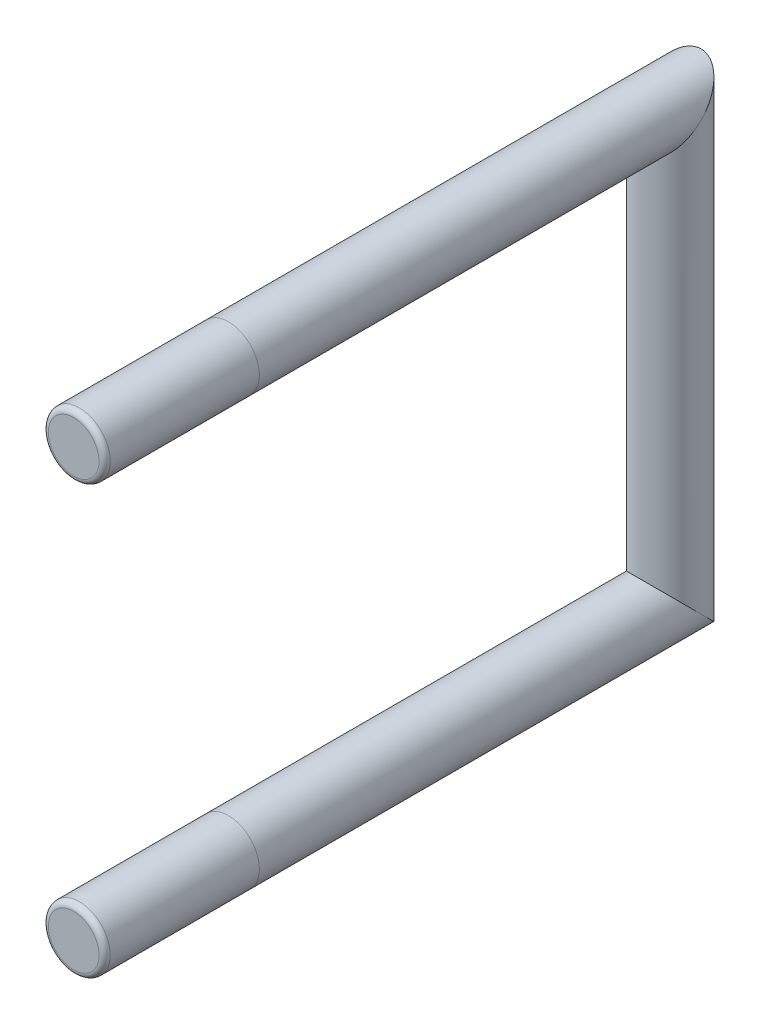
SolidWorks part; units mm, degrees
ref_plane "前视基准面" through (0, 0, 0) normal (0, 0, 1) x (1, 0, 0)
ref_plane "上视基准面" through (0, 0, 0) normal (0, 1, 0) x (1, 0, 0)
ref_plane "右视基准面" through (0, 0, 0) normal (1, 0, 0) x (0, 0, -1)
sketch "草图1" plane through (0, 0, 0) normal (0, 0, 1) x (1, 0, 0)
  circle A0 centre (0, 0) radius 11
  dimension "D1" = 22
extrude "拉伸1" add sketch "草图1" along normal blind 157
sketch "草图2" plane through (0, 0, 0) normal (0, 1, 0) x (1, 0, 0)
  circle A0 centre (0, 0) radius 11
  dimension "D1" = 22
extrude "拉伸2" add sketch "草图2" along normal blind 152
ref_axis "基准轴1" through (0, 171.7544, 0) along (0, -1, 0)
pattern_linear "阵列(线性)1" count 2 spacing 152 along (0, 1, 0) of "拉伸1"
chamfer "倒角3" distance 21.999 angle 45 2 edges at (0, 0, 0) (0, 152, 0)
sketch "草图3" plane through (0, 0, 157) normal (0, 0, 1) x (1, 0, 0)
  circle A0 centre (0, 152) radius 10.9995
  circle A1 centre (0, 0) radius 10.9995
  circle A2 centre (0, 152) radius 11 construction
  dimension "D1" = 21.999
extrude "拉伸3" add sketch "草图3" along normal blind 55
fillet "圆角1" radius 2 2 edges at (10.9995, 0, 212) (10.9995, 152, 212)
